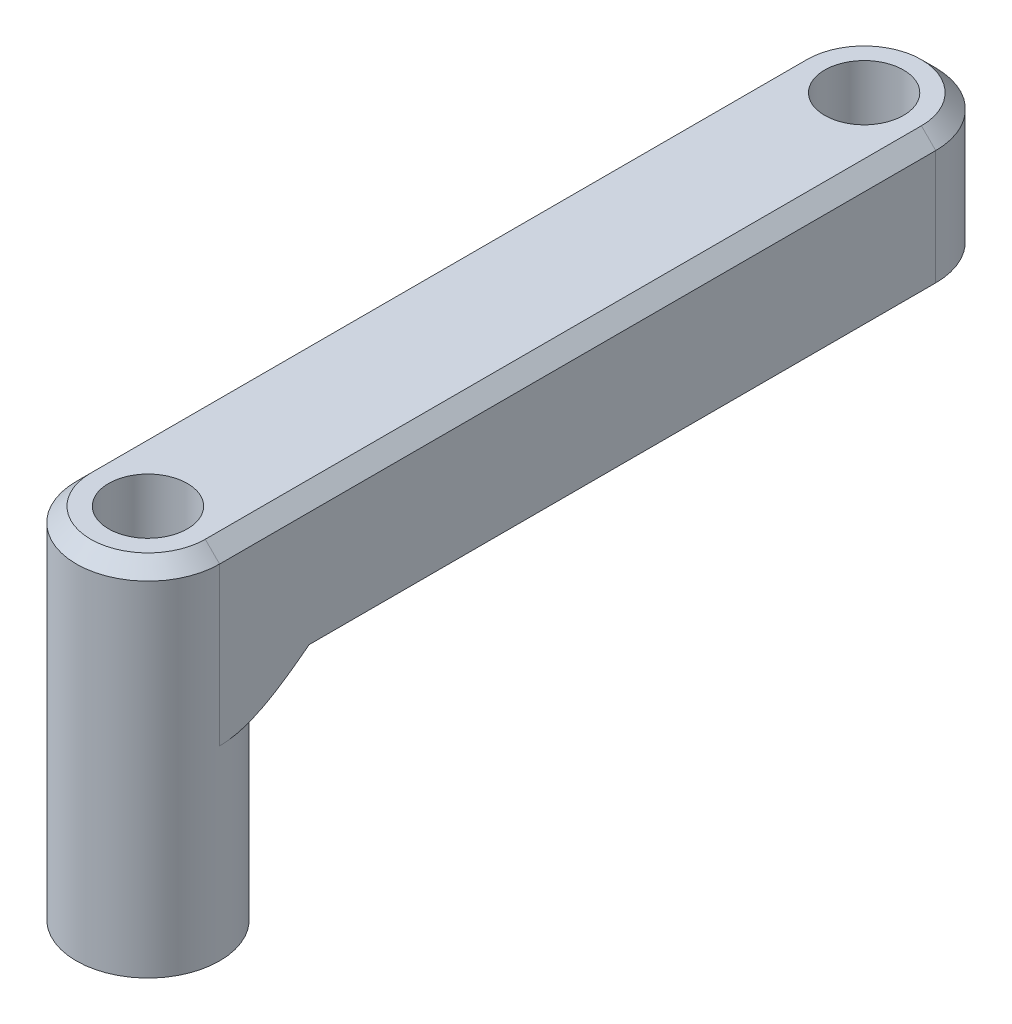
SolidWorks part; units mm, degrees
ref_plane "前视基准面" through (0, 0, 0) normal (0, 0, 1) x (1, 0, 0)
ref_plane "上视基准面" through (0, 0, 0) normal (0, 1, 0) x (1, 0, 0)
ref_plane "右视基准面" through (0, 0, 0) normal (1, 0, 0) x (0, 0, -1)
other "Configuration Table"
sketch "草图1" plane through (0, 0, 0) normal (0, 1, 0) x (1, 0, 0)
  line L0 (0, 0) -> (0, 50) construction
  line L1 (5, 0) -> (5, 50)
  line L2 (-5, 50) -> (-5, 0)
  arc A0 (-5, 0) -> (5, 0) centre (0, 0) ccw
  arc A1 (5, 50) -> (-5, 50) centre (0, 50) ccw
  dimension "D1" = 10
  dimension "D2" = 10
  dimension "D3" = 50
extrude "凸台-拉伸1" add sketch "草图1" along normal blind 10
sketch "草图3" plane through (0, 0, 0) normal (0, 1, 0) x (1, 0, 0)
  circle A0 centre (0, 0) radius 5
extrude "凸台-拉伸2" add sketch "草图3" against normal blind 15
sketch "草图4" plane through (0, 0, 0) normal (0, 1, 0) x (1, 0, 0)
  circle A0 centre (0, 0) radius 2.75
  dimension "D1" = 5.5
extrude "切除-拉伸1" cut sketch "草图4" against normal up to surface (15 mm away) from surface up to face at (0, -15, 5) starting at face at (0, 10, -25)
sketch "草图5" plane through (0, 0, 0) normal (0, 1, 0) x (1, 0, 0)
  circle A0 centre (0, 50) radius 2.75
  dimension "D1" = 5.5
extrude "切除-拉伸2" cut sketch "草图5" against normal up to surface from surface up to face at (0, 0, -27.5) starting at face at (0, 10, 2.75)
chamfer "倒角1" distance 2 angle 45 1 edges at (0, 0, -5)
chamfer "倒角2" distance 1 angle 45 7 edges at (0, 10, -55) (-5, 10, -25) (0, 10, 5) (5, 10, -25) (-5, 0, -27.4495) (0, 0, -55) (5, 0, -27.4495)
